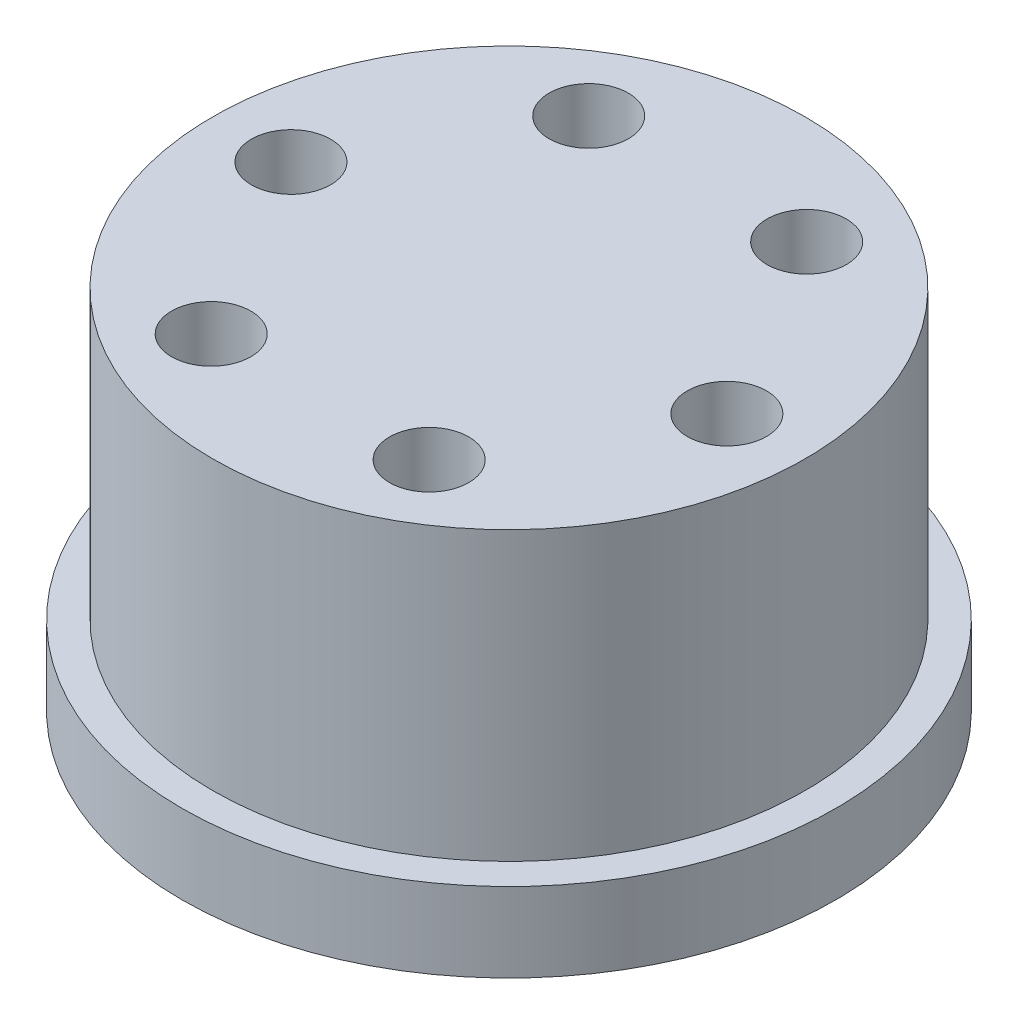
SolidWorks part; units mm, degrees
ref_plane "Front Plane" through (0, 0, 0) normal (0, 0, 1) x (1, 0, 0)
ref_plane "Top Plane" through (0, 0, 0) normal (0, 1, 0) x (1, 0, 0)
ref_plane "Right Plane" through (0, 0, 0) normal (1, 0, 0) x (0, 0, -1)
sketch "Sketch1" plane through (0, 0, 0) normal (0, 1, 0) x (1, 0, 0)
  circle A0 centre (0, 0) radius 16.5
  circle A1 centre (0, 0) radius 12.5 construction
  circle A2 centre (0, 12.5) radius 1.75
  circle A3 centre (10.8253, 6.25) radius 1.75
  circle A4 centre (10.8253, -6.25) radius 1.75
  circle A5 centre (0, -12.5) radius 1.75
  circle A6 centre (-10.8253, -6.25) radius 1.75
  circle A7 centre (-10.8253, 6.25) radius 1.75
  point P19 (0, 0)
  dimension "D1" = 33
  dimension "D2" = 25
  dimension "D3" = 3.5
  dimension "D4" = 6
extrude "Boss-Extrude1" add sketch "Sketch1" along normal blind 4
sketch "Sketch2" plane through (0, 4, 0) normal (0, 1, 0) x (1, 0, 0)
  circle A0 centre (0, 0) radius 14.95
  dimension "D1" = 29.9
extrude "Boss-Extrude2" add sketch "Sketch2" along normal blind 14.5
sketch "Sketch5" plane through (0, 18.5, 0) normal (0, 1, 0) x (1, 0, 0)
  circle A0 centre (0, 0) radius 11 construction
  circle A1 centre (-11, 0) radius 2
  circle A2 centre (-5.5, 9.5263) radius 2
  circle A3 centre (5.5, 9.5263) radius 2
  circle A4 centre (11, 0) radius 2
  circle A5 centre (5.5, -9.5263) radius 2
  circle A6 centre (-5.5, -9.5263) radius 2
  point P17 (0, 0)
  dimension "D1" = 22
  dimension "D2" = 4
  dimension "D3" = 6
extrude "Cut-Extrude3" cut sketch "Sketch5" against normal blind 6.5
sketch "Sketch6" plane through (0, 0, 0) normal (0, -1, 0) x (1, 0, 0)
  circle A0 centre (0, 0) radius 7.6
  dimension "D1" = 15.2
extrude "Cut-Extrude4" cut sketch "Sketch6" against normal blind 5
